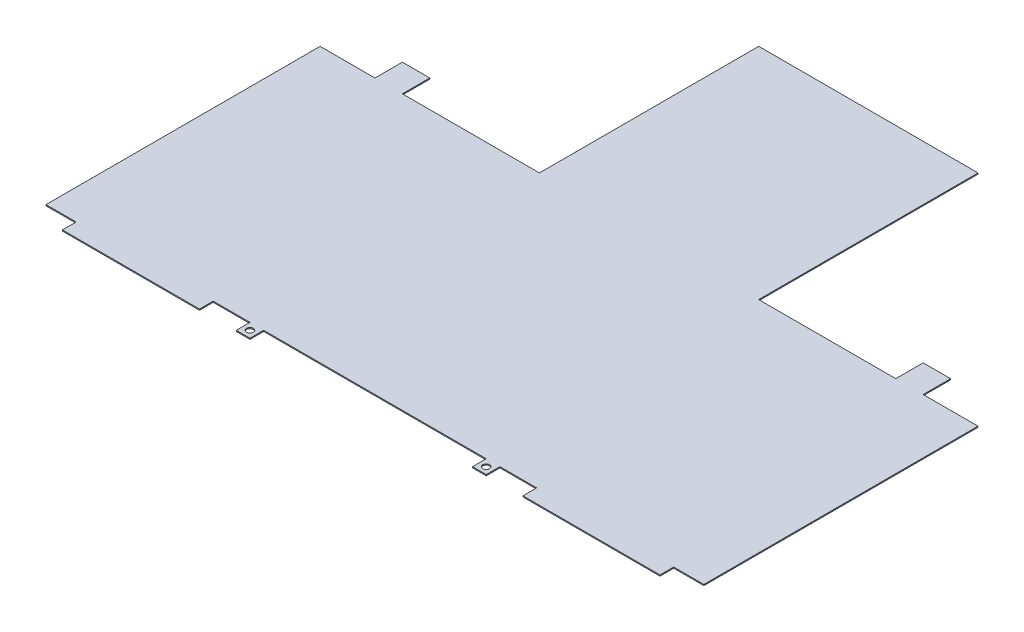
SolidWorks part; units mm, degrees
ref_plane "Front Plane" through (0, 0, 0) normal (0, 0, 1) x (1, 0, 0)
ref_plane "Top Plane" through (0, 0, 0) normal (0, 1, 0) x (1, 0, 0)
ref_plane "Right Plane" through (0, 0, 0) normal (1, 0, 0) x (0, 0, -1)
sketch "Sketch1" plane through (0, 0, 0) normal (0, 1, 0) x (1, 0, 0)
  line L1 (-304.8, -127) -> (304.8, -127)
  line L2 (-304.8, -127) -> (-304.8, 127)
  line L3 (-304.8, 127) -> (304.8, 127)
  line L4 (304.8, -127) -> (304.8, 127)
  line L5 (-304.8, -127) -> (304.8, 127) construction
  line L6 (-304.8, 127) -> (304.8, -127) construction
  point P0 (0, 0)
  dimension "D1" = 609.6
  dimension "D2" = 254
base flange "Base-Flange1" sketch "Sketch1" thickness 1 reverse thickness direction no parameters "D1"=1
sketch "Sketch6" plane through (0, 0, 0) normal (0, 1, 0) x (1, 0, 0)
  line L0 (304.8, 127) -> (-304.8, 127) construction
  line L1 (-254, 152.4) -> (-228.6, 152.4)
  line L2 (-254, 152.4) -> (-254, 127)
  line L3 (-254, 127) -> (-228.6, 127)
  line L4 (-228.6, 152.4) -> (-228.6, 127)
  dimension "D1" = 25.4
  dimension "D2" = 25.4
  dimension "D3" = 254
base flange "Tab2" sketch "Sketch6" thickness 1 reverse thickness direction no parameters "D1"=1
sketch "Sketch11" plane through (0, 0, 0) normal (0, 1, 0) x (1, 0, 0)
  line L0 (304.8, 127) -> (-228.6, 127) construction
  line L1 (228.6, 152.4) -> (254, 152.4)
  line L2 (228.6, 152.4) -> (228.6, 127)
  line L3 (228.6, 127) -> (254, 127)
  line L4 (254, 152.4) -> (254, 127)
  dimension "D1" = 25.4
  dimension "D2" = 25.4
  dimension "D3" = 254
base flange "Tab3" sketch "Sketch11" thickness 1 reverse thickness direction no parameters "D1"=1
sketch "Sketch14" plane through (0, 0, 0) normal (0, 1, 0) x (1, 0, 0)
  line L0 (228.6, 127) -> (-228.6, 127) construction
  line L1 (-101.6, 330.2) -> (101.6, 330.2)
  line L2 (-101.6, 330.2) -> (-101.6, 127)
  line L3 (-101.6, 127) -> (101.6, 127)
  line L4 (101.6, 330.2) -> (101.6, 127)
  dimension "D1" = 203.2
  dimension "D2" = 203.2
  dimension "D3" = 101.6
base flange "Tab4" sketch "Sketch14" thickness 1 reverse thickness direction no parameters "D1"=1
sketch "Sketch17" plane through (0, 0, 0) normal (0, 1, 0) x (1, 0, 0)
  line L0 (-304.8, -127) -> (304.8, -127) construction
  line L1 (-149.86, -139.7) -> (-276.86, -139.7)
  line L2 (-149.86, -139.7) -> (-149.86, -127)
  line L3 (-149.86, -127) -> (-276.86, -127)
  line L4 (-276.86, -139.7) -> (-276.86, -127)
  line L5 (-101.6, 330.2) -> (-101.6, 127) construction
  dimension "D1" = 127
  dimension "D2" = 12.7
  dimension "D3" = 48.26
base flange "Tab5" sketch "Sketch17" thickness 1 reverse thickness direction no parameters "D1"=1
sketch "Sketch20" plane through (0, 0, 0) normal (0, 1, 0) x (1, 0, 0)
  line L0 (-149.86, -127) -> (304.8, -127) construction
  line L1 (149.86, -127) -> (276.86, -127)
  line L2 (149.86, -127) -> (149.86, -139.7)
  line L3 (149.86, -139.7) -> (276.86, -139.7)
  line L4 (276.86, -127) -> (276.86, -139.7)
  dimension "D1" = 127
  dimension "D2" = 12.7
base flange "Tab7" sketch "Sketch20" thickness 1 reverse thickness direction no parameters "D1"=1
sketch "Sketch25" plane through (0, 0, 0) normal (0, 1, 0) x (1, 0, 0)
  line L0 (-149.86, -127) -> (149.86, -127) construction
  line L1 (-115.8, -127) -> (-103.1, -127)
  line L2 (-115.8, -127) -> (-115.8, -139.7)
  line L3 (-115.8, -139.7) -> (-103.1, -139.7)
  line L4 (-103.1, -127) -> (-103.1, -139.7)
  line L5 (-101.6, 330.2) -> (-101.6, 127) construction
  dimension "D1" = 12.7
  dimension "D2" = 12.7
  dimension "D3" = 1.5
base flange "Tab8" sketch "Sketch25" thickness 1 reverse thickness direction no parameters "D1"=1
sketch "Sketch28" plane through (0, 0, 0) normal (0, 1, 0) x (1, 0, 0)
  line L0 (-103.1, -127) -> (149.86, -127) construction
  line L1 (103.1, -127) -> (115.8, -127)
  line L2 (103.1, -127) -> (103.1, -139.7)
  line L3 (103.1, -139.7) -> (115.8, -139.7)
  line L4 (115.8, -127) -> (115.8, -139.7)
  line L5 (101.6, 127) -> (101.6, 330.2) construction
  dimension "D1" = 12.7
  dimension "D2" = 12.7
  dimension "D3" = 1.5
base flange "Tab10" sketch "Sketch28" thickness 1 reverse thickness direction no parameters "D1"=1
sketch "Sketch36" plane through (0, 0, 0) normal (0, 1, 0) x (1, 0, 0)
  line L0 (-103.1, -139.7) -> (-103.1, -127) construction
  line L2 (-115.8, -139.7) -> (-103.1, -139.7) construction
  circle A0 centre (-109.45, -133.35) radius 3.15
  dimension "D1" = 6.35
  dimension "D2" = 6.3
  dimension "D3" = 6.35
extrude "Cut-Extrude2" cut sketch "Sketch36" against normal through all normal cut yes
sketch "Sketch38" plane through (0, 0, 0) normal (0, 1, 0) x (1, 0, 0)
  line L0 (115.8, -139.7) -> (115.8, -127) construction
  line L2 (103.1, -139.7) -> (115.8, -139.7) construction
  circle A0 centre (109.45, -133.35) radius 3.15
  dimension "D1" = 6.35
  dimension "D3" = 6.3
  dimension "D2" = 6.35
extrude "Cut-Extrude3" cut sketch "Sketch38" against normal through all normal cut yes
sketch "Bend-Lines1" [suppressed] plane through (0, 0, 0) normal (0, 1, 0) x (1, 0, 0)
sketch "Bounding-Box1" [suppressed] plane through (0, 0, 0) normal (0, 1, 0) x (1, 0, 0)
sheet metal parameters "Sheet-Metal1" thickness 1 parameters "D1"=1
flat pattern "Flat-Pattern1" [suppressed]
sketch "Bend-Lines2" plane through (0, 0, 0) normal (0, 1, 0) x (1, 0, 0)
sketch "Bounding-Box2" [suppressed] plane through (0, 0, 0) normal (0, 1, 0) x (1, 0, 0)
sheet metal parameters "Sheet-Metal3" thickness 1 parameters "D1"=1
flat pattern "Flat-Pattern3"
sketch "Bend-Lines4" plane through (0, 0, 0) normal (0, 1, 0) x (1, 0, 0)
sketch "Bounding-Box4" [suppressed] plane through (0, 0, 0) normal (0, 1, 0) x (1, 0, 0)
sheet metal parameters "Sheet-Metal4" thickness 1 parameters "D1"=1
flat pattern "Flat-Pattern4"
sketch "Bend-Lines5" plane through (0, 0, 0) normal (0, 1, 0) x (1, 0, 0)
sketch "Bounding-Box5" [suppressed] plane through (0, 0, 0) normal (0, 1, 0) x (1, 0, 0)
sheet metal parameters "Sheet-Metal5" thickness 1 parameters "D1"=1
flat pattern "Flat-Pattern5"
sketch "Bend-Lines6" plane through (0, 0, 0) normal (0, 1, 0) x (1, 0, 0)
sketch "Bounding-Box6" [suppressed] plane through (0, 0, 0) normal (0, 1, 0) x (1, 0, 0)
sheet metal parameters "Sheet-Metal6" thickness 1 parameters "D1"=1
flat pattern "Flat-Pattern6"
sketch "Bend-Lines7" plane through (0, 0, 0) normal (0, 1, 0) x (1, 0, 0)
sketch "Bounding-Box7" [suppressed] plane through (0, 0, 0) normal (0, 1, 0) x (1, 0, 0)
sheet metal parameters "Sheet-Metal8" thickness 1 parameters "D1"=1
flat pattern "Flat-Pattern8"
sketch "Bend-Lines9" plane through (0, 0, 0) normal (0, 1, 0) x (1, 0, 0)
sketch "Bounding-Box9" [suppressed] plane through (0, 0, 0) normal (0, 1, 0) x (1, 0, 0)
sheet metal parameters "Sheet-Metal9" thickness 1 parameters "D1"=1
flat pattern "Flat-Pattern9"
sketch "Bend-Lines10" plane through (0, 0, 0) normal (0, 1, 0) x (1, 0, 0)
sketch "Bounding-Box10" [suppressed] plane through (0, 0, 0) normal (0, 1, 0) x (1, 0, 0)
sheet metal parameters "Sheet-Metal11" thickness 1 parameters "D1"=1
flat pattern "Flat-Pattern11"
sketch "Bend-Lines12" plane through (0, 0, 0) normal (0, 1, 0) x (1, 0, 0)
sketch3d "Bounding-Box12" [suppressed]
  line L0 (304.8, 330.2, 0) -> (-304.8, 330.2, 0) construction
  line L1 (304.8, -139.7, 0) -> (-304.8, -139.7, 0) construction
  line L2 (304.8, 330.2, 0) -> (304.8, -139.7, 0) construction
  line L3 (-304.8, 330.2, 0) -> (-304.8, -139.7, 0) construction
sheet metal parameters "Sheet-Metal13" thickness 1 parameters "D1"=1
flat pattern "Flat-Pattern11"
sketch "Bend-Lines12" plane through (0, 0, 0) normal (0, 1, 0) x (1, 0, 0)
sketch3d "Bounding-Box12" [suppressed]
  line L0 (304.8, 330.2, 0) -> (-304.8, 330.2, 0) construction
  line L1 (304.8, -139.7, 0) -> (-304.8, -139.7, 0) construction
  line L2 (304.8, 330.2, 0) -> (304.8, -139.7, 0) construction
  line L3 (-304.8, 330.2, 0) -> (-304.8, -139.7, 0) construction
sheet metal parameters "Sheet-Metal14" thickness 1 parameters "D1"=1
flat pattern "Flat-Pattern11"
sketch "Bend-Lines12" plane through (0, 0, 0) normal (0, 1, 0) x (1, 0, 0)
sketch3d "Bounding-Box12" [suppressed]
  line L0 (304.8, 330.2, 0) -> (-304.8, 330.2, 0) construction
  line L1 (304.8, -139.7, 0) -> (-304.8, -139.7, 0) construction
  line L2 (304.8, 330.2, 0) -> (304.8, -139.7, 0) construction
  line L3 (-304.8, 330.2, 0) -> (-304.8, -139.7, 0) construction
